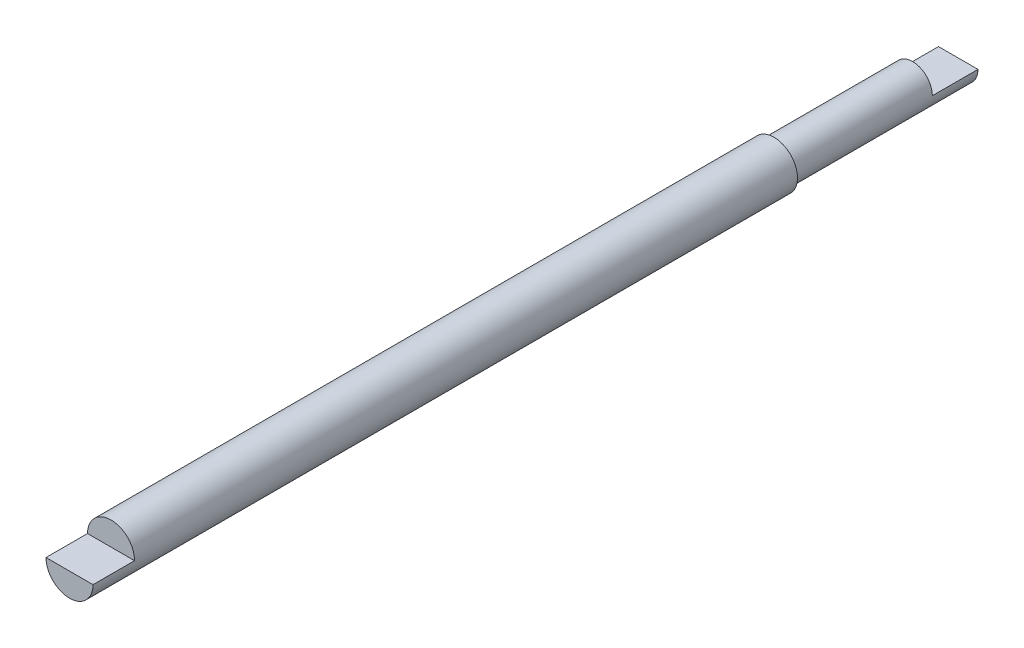
SolidWorks part; units mm, degrees
ref_plane "Front Plane" through (0, 0, 0) normal (0, 0, 1) x (1, 0, 0)
ref_plane "Top Plane" through (0, 0, 0) normal (0, 1, 0) x (1, 0, 0)
ref_plane "Right Plane" through (0, 0, 0) normal (1, 0, 0) x (0, 0, -1)
sketch "Sketch1" plane through (0, 0, 0) normal (0, 0, 1) x (1, 0, 0)
  circle A0 centre (0, 0) radius 4.7625
  dimension "D1" = 9.525
extrude "Boss-Extrude1" add sketch "Sketch1" along normal blind 180
sketch "Sketch2" plane through (0, 0, 180) normal (0, 0, 1) x (1, 0, 0)
  line L1 (-4.7625, 0) -> (4.7625, 0)
  circle A0 centre (0, 0) radius 4.7625
  circle M2 centre (0, 0) radius 4.7625
  dimension "D2" = 9.525
extrude "Cut-Extrude1" cut sketch "Sketch2" against normal blind 8.41 contours M2 region at (0, 2.0213, 180)
sketch "Sketch3" plane through (0, 0, 0) normal (0, 0, -1) x (-1, 0, 0)
  circle A0 centre (0, 0) radius 4.7625
  circle A1 centre (0, 0) radius 4
  dimension "D1" = 9.525
  dimension "D2" = 8
extrude "Cut-Extrude2" cut sketch "Sketch3" against normal blind 37.32
sketch "Sketch4" plane through (0, 0, 0) normal (0, 0, -1) x (-1, 0, 0)
  line L0 (-4, 0) -> (4, 0)
  circle A0 centre (0, 0) radius 4
  circle M1 centre (0, 0) radius 4
  dimension "D1" = 8
extrude "Cut-Extrude3" cut sketch "Sketch4" against normal blind 9.25 contours L0 M1 region at (0, 1.6977, 0)
